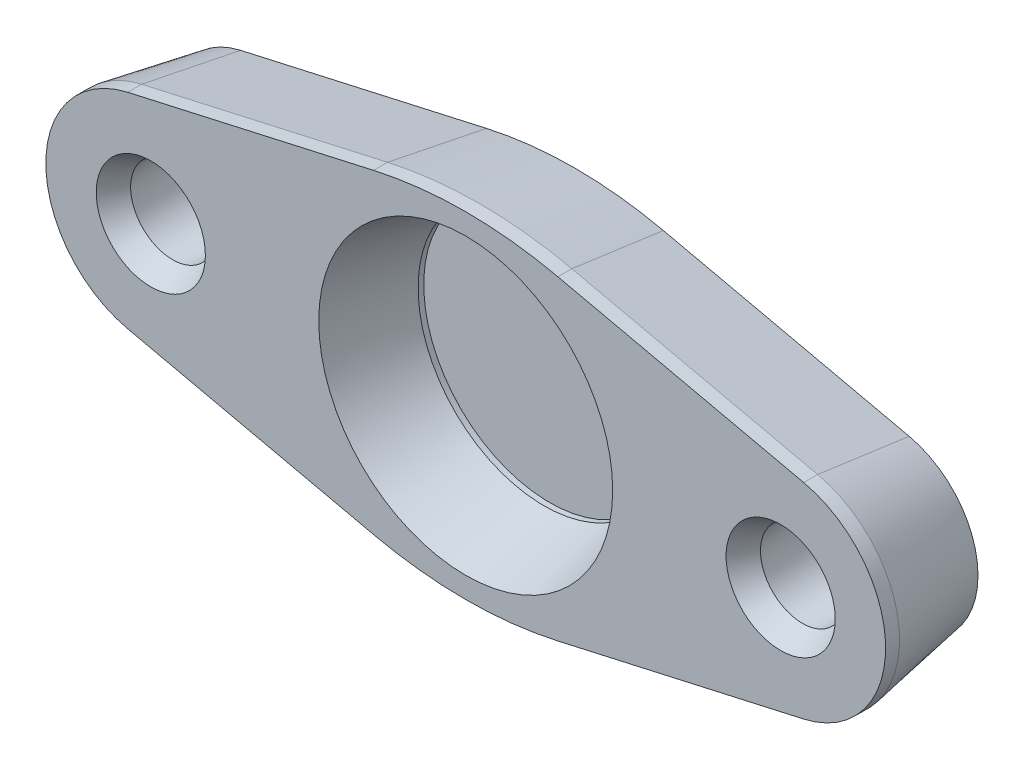
SolidWorks part; units mm, degrees
ref_plane "Front Plane" through (0, 0, 0) normal (0, 0, 1) x (1, 0, 0)
ref_plane "Top Plane" through (0, 0, 0) normal (0, 1, 0) x (1, 0, 0)
ref_plane "Right Plane" through (0, 0, 0) normal (1, 0, 0) x (0, 0, -1)
sketch "Sketch1" plane through (0, 0, 0) normal (0, 0, 1) x (1, 0, 0)
  line L0 (-8.0488, 2.439) -> (-2.1951, 3.7561)
  line L1 (2.1951, 3.7561) -> (8.0488, 2.439)
  line L2 (-8.0488, -2.439) -> (-2.1951, -3.7561)
  line L3 (2.1951, -3.7561) -> (8.0488, -2.439)
  line L4 (0, 9.0509) -> (0, -9.0509) construction
  line L5 (-11.5511, 0) -> (12.1784, 0) construction
  circle A0 centre (0, 0) radius 3 construction
  circle A1 centre (7.5, 0) radius 1
  circle A2 centre (-7.5, 0) radius 1
  arc A3 (-8.0488, 2.439) -> (-8.0488, -2.439) centre (-7.5, 0) ccw
  arc A4 (8.0488, -2.439) -> (8.0488, 2.439) centre (7.5, 0) ccw
  arc A5 (-2.1951, -3.7561) -> (2.1951, -3.7561) centre (0, 6) ccw
  arc A6 (-2.1951, 3.7561) -> (2.1951, 3.7561) centre (0, -6) cw
  point P17 (0, -4.25)
  point P22 (0, 4.25)
  dimension "D1" = 2
  dimension "D2" = 15
  dimension "D3" = 5
  dimension "D4" = 6
  dimension "D5" = 10
  dimension "D6" = 6
extrude "Boss-Extrude1" add sketch "Sketch1" along normal blind 2.6
sketch "Sketch2" plane through (0, 0, 2.6) normal (0, 0, 1) x (1, 0, 0)
  circle A0 centre (0, 0) radius 3
  dimension "D1" = 6
extrude "Cut-Extrude1" cut sketch "Sketch2" against normal blind 2
chamfer "Chamfer1" distance 0.4 angle 80 8 edges at (-5.122, 3.0976, 0) (-10, 0, 0) (0, 4, 0) (-5.122, -3.0976, 0) (5.122, 3.0976, 0) (0, -4, 0) (10, 0, 0) (5.122, -3.0976, 0) first distance on face at (0, 0, 0)
chamfer "Chamfer2" distance 0.5 angle 75 1 edges at (3, 0, 2.6) first distance on face at (3, 0, 2.6)
chamfer "Chamfer3" distance 0.3 angle 60 2 edges at (8.5, 0, 2.6) (-6.5, 0, 2.6) first distance on face at (3.5, 0, 2.6)
